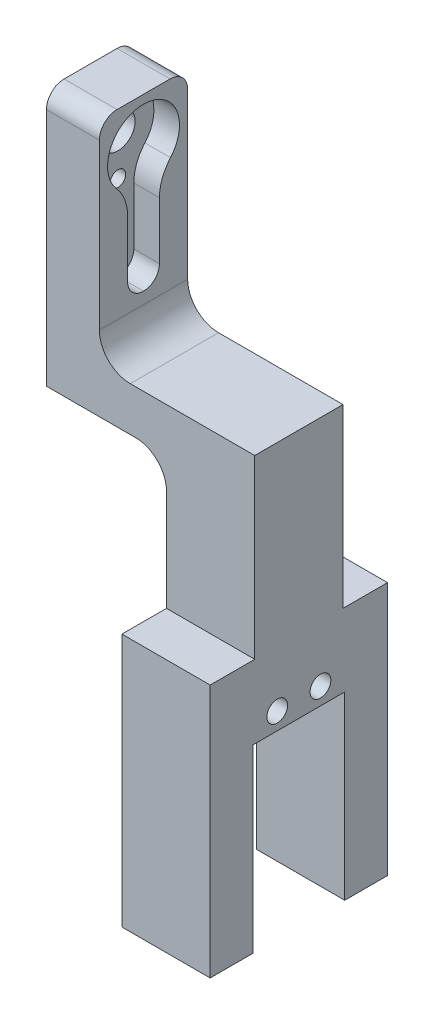
SolidWorks part; units mm, degrees
ref_plane "Front Plane" through (0, 0, 0) normal (0, 0, 1) x (1, 0, 0)
ref_plane "Top Plane" through (0, 0, 0) normal (0, 1, 0) x (1, 0, 0)
ref_plane "Right Plane" through (0, 0, 0) normal (1, 0, 0) x (0, 0, -1)
sketch "Sketch1" plane through (0, 0, 0) normal (1, 0, 0) x (0, 0, -1)
  line L1 (-10, 10) -> (10, 10)
  line L2 (-10, 10) -> (-10, -10)
  line L3 (-10, -10) -> (10, -10)
  line L4 (10, 10) -> (10, -10)
  line L5 (-10, 10) -> (10, -10) construction
  line L6 (-10, -10) -> (10, 10) construction
  point P0 (0, 0)
  dimension "D1" = 20
  dimension "D2" = 20
extrude "Boss-Extrude1" add sketch "Sketch1" along normal blind 20
sketch "Sketch2" plane through (20, 0, 0) normal (1, 0, 0) x (0, 0, -1)
  line L1 (-22.5, 35) -> (22.5, 35)
  line L2 (-22.5, 35) -> (-22.5, -35)
  line L3 (-22.5, -35) -> (22.5, -35)
  line L4 (22.5, 35) -> (22.5, -35)
  line L5 (-22.5, 35) -> (22.5, -35) construction
  line L6 (-22.5, -35) -> (22.5, 35) construction
  point P0 (0, 0)
  dimension "D1" = 45
  dimension "D2" = 70
extrude "Boss-Extrude2" add sketch "Sketch2" along normal blind 12
sketch "Sketch4" plane through (32, 0, 0) normal (1, 0, 0) x (0, 0, -1)
  line L0 (0, 7.65) -> (0, 8.1702) construction
  line L1 (7.65, 7.65) -> (-7.65, 7.65) construction
  line L17 (3.6, -26.55) -> (-3.6, -26.55) construction
  line L18 (-7.65, 7.65) -> (7.65, 7.65) construction
  line L22 (-7.65, 7.65) -> (-7.65, -27.55) construction
  line L23 (-7.65, -27.55) -> (7.65, -27.55) construction
  line L24 (7.65, 7.65) -> (7.65, -27.55) construction
  line L25 (-7.65, 7.65) -> (7.65, -27.55) construction
  line L26 (-7.65, -27.55) -> (7.65, 7.65) construction
  line L27 (3.6, -26.55) -> (3.6, -28.55) construction
  line L28 (3.6, -28.55) -> (-3.6, -28.55) construction
  line L29 (-3.6, -26.55) -> (-3.6, -28.55) construction
  line L30 (3.6, -26.55) -> (-3.6, -28.55) construction
  line L31 (3.6, -28.55) -> (-3.6, -26.55) construction
  line L34 (3.6, -28.55) -> (-3.6, -28.55)
  line L35 (-3.6, -28.55) -> (-3.6, -7.3118)
  line L36 (3.6, -28.55) -> (3.6, -7.3118)
  arc A1 (3.6, -6.75) -> (-3.6, -6.75) centre (0, 0) ccw construction
  arc A2 (3.6, -7.3118) -> (-3.6, -7.3118) centre (0, 0) ccw
  point P1 (0, -27.55)
  point P7 (0, -13.75)
  point P10 (0, 7.65)
  point P14 (0, -9.95)
  dimension "D1" = 15.3
  dimension "D5" = 2
  dimension "D2" = 15.3
  dimension "D3" = 35.2
  dimension "D4" = 7.2
extrude "Cut-Extrude1" cut sketch "Sketch4" against normal blind 5.8
fillet "Fillet1" radius 3.6 2 edges at (29.1, -28.55, 3.6) (29.1, -28.55, -3.6)
fillet "Fillet2" radius 10 2 edges at (29.1, -7.3118, 3.6) (29.1, -7.3118, -3.6)
sketch "Sketch5" plane through (0, 0, 0) normal (-1, 0, 0) x (0, 0, 1)
  circle A0 centre (0, 0) radius 3.9
  dimension "D1" = 7.8
extrude "Cut-Extrude2" cut sketch "Sketch5" against normal through all
sketch "Sketch6" plane through (26.2, 0, 0) normal (1, 0, 0) x (0, 0, -1)
  line L0 (0, -19.35) -> (0, 0) construction
  line L1 (0, -25.65) -> (0, -23.15) construction
  line L2 (0, -23.15) -> (0, -21.85) construction
  line L3 (0, -21.85) -> (0, -19.35) construction
  line L5 (0, 0) -> (1.164, 0) construction
  line L6 (0, 0) -> (0, -9.35) construction
  line L7 (0, -9.35) -> (1.164, -9.35) construction
  line L8 (1.164, 0) -> (1.164, -9.35) construction
  line L9 (0, 0) -> (1.164, -9.35) construction
  line L10 (0, -9.35) -> (1.164, 0) construction
  circle A0 centre (0, -20.6) radius 1.75
  circle A1 centre (0, -9.35) radius 1.75
  point P11 (0.582, -4.675)
  dimension "D5" = 3.5
  dimension "D6" = 9.35
  dimension "D7" = 3.5
  dimension "D1" = 19.35
  dimension "D2" = 2.5
  dimension "D3" = 1.3
  dimension "D4" = 2.5
extrude "Cut-Extrude3" cut sketch "Sketch6" against normal up to next
sketch "Sketch7" plane through (0, -35, 0) normal (0, -1, 0) x (1, 0, 0)
  line L1 (32, 22.5) -> (20, 22.5)
  line L2 (32, 22.5) -> (32, -22.5)
  line L3 (32, -22.5) -> (20, -22.5)
  line L4 (20, 22.5) -> (20, -22.5)
  line L5 (32, 22.5) -> (20, -22.5) construction
  line L6 (32, -22.5) -> (20, 22.5) construction
  point P5 (26, 0)
extrude "Cut-Extrude4" cut sketch "Sketch7" against normal blind 4.8
sketch "Sketch9" plane through (0, 35, 0) normal (0, 1, 0) x (1, 0, 0)
  line L1 (32, 22.5) -> (20, 22.5)
  line L2 (32, 22.5) -> (32, -22.5)
  line L3 (32, -22.5) -> (20, -22.5)
  line L4 (20, 22.5) -> (20, -22.5)
  line L5 (32, 22.5) -> (20, -22.5) construction
  line L6 (32, -22.5) -> (20, 22.5) construction
  point P4 (26, 0)
extrude "Cut-Extrude5" cut sketch "Sketch9" against normal blind 23.8
sketch "Sketch10" plane through (20, 0, 0) normal (-1, 0, 0) x (0, 0, 1)
  line L0 (-22.5, 11.2) -> (22.5, 11.2) construction
  line L1 (-10, 11.2) -> (-22.5, 11.2)
  line L2 (-10, 11.2) -> (-10, -30.2)
  line L3 (-10, -30.2) -> (-22.5, -30.2)
  line L4 (-22.5, 11.2) -> (-22.5, -30.2)
  line L5 (-10, 11.2) -> (-22.5, -30.2) construction
  line L6 (-10, -30.2) -> (-22.5, 11.2) construction
  line L7 (22.5, -30.2) -> (-22.5, -30.2) construction
  line L9 (10, 11.2) -> (22.5, 11.2)
  line L10 (10, 11.2) -> (10, -30.2)
  line L11 (10, -30.2) -> (22.5, -30.2)
  line L12 (22.5, 11.2) -> (22.5, -30.2)
  line L13 (10, 11.2) -> (22.5, -30.2) construction
  line L14 (10, -30.2) -> (22.5, 11.2) construction
  point P4 (-16.25, -9.5)
  point P13 (16.25, -9.5)
extrude "Cut-Extrude6" cut sketch "Sketch10" against normal blind 23.8
sketch "Sketch11" plane through (20, 0, 0) normal (-1, 0, 0) x (0, 0, 1)
  line L5 (-10, 11.2) -> (10, 11.2)
  line L6 (-10, 11.2) -> (-10, 10)
  line L7 (-10, 10) -> (10, 10)
  line L8 (10, 11.2) -> (10, 10)
  line L9 (-10, 11.2) -> (10, 10) construction
  line L10 (-10, 10) -> (10, 11.2) construction
  point P4 (0, 10.6)
extrude "Cut-Extrude7" cut sketch "Sketch11" against normal blind 23.8
sketch "Sketch12" plane through (0, 0, 0) normal (-1, 0, 0) x (0, 0, 1)
  line L1 (10, 10) -> (-10, 10)
  line L2 (10, 10) -> (10, -10)
  line L3 (10, -10) -> (-10, -10)
  line L4 (-10, 10) -> (-10, -10)
  line L5 (10, 10) -> (-10, -10) construction
  line L6 (10, -10) -> (-10, 10) construction
  circle A0 centre (0, 0) radius 3.9
  point P4 (0, 0)
extrude "Boss-Extrude3" add sketch "Sketch12" along normal blind 20
sketch "Sketch13" plane through (-20, 0, 0) normal (-1, 0, 0) x (0, 0, 1)
  line L8 (10.1, -10.1) -> (10.1, 10.1)
  line L9 (10.1, 10.1) -> (-10.1, 10.1)
  line L10 (-10.1, 10.1) -> (-10.1, -10.1)
  line L11 (-10.1, -10.1) -> (10.1, -10.1)
  line L12 (10.1, -10.1) -> (10.1, 10.1)
  line L13 (10.1, 10.1) -> (-10.1, 10.1)
  line L14 (-10.1, 10.1) -> (-10.1, -10.1)
  line L15 (-10.1, -10.1) -> (10.1, -10.1)
  circle A0 centre (0, 0) radius 3.9
  dimension "D1" = 0.1
extrude "Boss-Extrude4" add sketch "Sketch13" against normal up to surface (40 mm away) up to face at (20, -20.6, -1.75)
sketch "Sketch14" plane through (0, 10, 0) normal (0, 1, 0) x (1, 0, 0)
  line L1 (32, 10) -> (20, 10)
  line L2 (32, 10) -> (32, -10)
  line L3 (32, -10) -> (20, -10)
  line L4 (20, 10) -> (20, -10)
  line L5 (32, 10) -> (20, -10) construction
  line L6 (32, -10) -> (20, 10) construction
  point P4 (26, 0)
extrude "Boss-Extrude5" add sketch "Sketch14" along normal blind 0.1
sketch "Sketch17" plane through (-20, 0, 0) normal (-1, 0, 0) x (0, 0, 1)
  circle A0 centre (0, 0) radius 4.8309
extrude "Boss-Extrude8" add sketch "Sketch17" against normal blind 39
sketch "Sketch18" plane through (-20, 0, 0) normal (-1, 0, 0) x (0, 0, 1)
  line L1 (10.1, 10.1) -> (-10.1, 10.1)
  line L2 (10.1, 10.1) -> (10.1, -10.1)
  line L3 (10.1, -10.1) -> (-10.1, -10.1)
  line L4 (-10.1, 10.1) -> (-10.1, -10.1)
  line L5 (10.1, 10.1) -> (-10.1, -10.1) construction
  line L6 (10.1, -10.1) -> (-10.1, 10.1) construction
  point P4 (0, 0)
extrude "Cut-Extrude8" cut sketch "Sketch18" against normal up to surface (40 mm away) up to face at (20, -20.6, -1.75)
fillet "Fillet4" radius 4 2 edges at (26, 10.1, -10) (26, 10.1, 10)
sketch "Sketch20" plane through (0, -30.2, 0) normal (0, -1, 0) x (1, 0, 0)
  line L6 (20, 10) -> (32, 10)
  line L9 (20, 10) -> (20, -10)
  line L10 (20, -10) -> (32, -10)
  line L11 (32, 10) -> (32, -10)
  line L12 (20, 10) -> (32, -10) construction
  line L13 (20, -10) -> (32, 10) construction
  point P4 (26, 0)
extrude "Boss-Extrude9" add sketch "Sketch20" along normal blind 8
sketch "Sketch21" plane through (0, -38.2, 0) normal (0, -1, 0) x (1, 0, 0)
  line L5 (20, 10) -> (67.2, 10)
  line L6 (20, 10) -> (20, -10)
  line L7 (20, -10) -> (67.2, -10)
  line L8 (67.2, 10) -> (67.2, -10)
  line L9 (20, 10) -> (67.2, -10) construction
  line L10 (20, -10) -> (67.2, 10) construction
  point P4 (43.6, 0)
  dimension "D1" = 47.2
extrude "Boss-Extrude11" add sketch "Sketch21" along normal blind 10
sketch "Sketch23" plane through (0, -48.2, 0) normal (0, -1, 0) x (1, 0, 0)
  line L0 (20, -10) -> (67.2, -10) construction
  line L1 (67.2, 10) -> (47.2, 10)
  line L2 (67.2, 10) -> (67.2, -10)
  line L3 (67.2, -10) -> (47.2, -10)
  line L4 (47.2, 10) -> (47.2, -10)
  line L5 (67.2, 10) -> (47.2, -10) construction
  line L6 (67.2, -10) -> (47.2, 10) construction
  point P4 (57.2, 0)
  dimension "D1" = 20
extrude "Boss-Extrude12" add sketch "Sketch23" along normal blind 30
sketch "Sketch25" plane through (0, -78.2, 0) normal (0, -1, 0) x (1, 0, 0)
  line L1 (67.2, 10) -> (47.2, 10) construction
  line L2 (67.2, 10) -> (67.2, -10) construction
  line L3 (67.2, -10) -> (47.2, -10) construction
  line L4 (47.2, 10) -> (47.2, -10) construction
  line L5 (67.2, 10) -> (47.2, -10) construction
  line L6 (67.2, -10) -> (47.2, 10) construction
  line L7 (67.2, 20.1) -> (47.2, 20.1)
  line L8 (67.2, 20.1) -> (67.2, -20.1)
  line L9 (67.2, -20.1) -> (47.2, -20.1)
  line L10 (47.2, 20.1) -> (47.2, -20.1)
  line L11 (67.2, 20.1) -> (47.2, -20.1) construction
  line L12 (67.2, -20.1) -> (47.2, 20.1) construction
  point P4 (57.2, 0)
  point P7 (57.2, 0)
  dimension "D1" = 40.2
extrude "Boss-Extrude13" add sketch "Sketch25" along normal blind 57.5
sketch "Sketch26" plane through (0, -135.7, 0) normal (0, -1, 0) x (1, 0, 0)
  line L1 (67.2, 20.1) -> (47.2, 20.1) construction
  line L2 (67.2, 20.1) -> (67.2, -20.1) construction
  line L3 (67.2, -20.1) -> (47.2, -20.1) construction
  line L4 (47.2, 20.1) -> (47.2, -20.1) construction
  line L5 (67.2, 20.1) -> (47.2, -20.1) construction
  line L6 (67.2, -20.1) -> (47.2, 20.1) construction
  line L7 (67.2, 10.4) -> (47.2, 10.4)
  line L8 (67.2, 10.4) -> (67.2, -10.4)
  line L9 (67.2, -10.4) -> (47.2, -10.4)
  line L10 (47.2, 10.4) -> (47.2, -10.4)
  line L11 (67.2, 10.4) -> (47.2, -10.4) construction
  line L12 (67.2, -10.4) -> (47.2, 10.4) construction
  point P4 (57.2, 0)
  point P7 (57.2, 0)
  dimension "D1" = 20.8
extrude "Cut-Extrude9" cut sketch "Sketch26" against normal blind 40.9
sketch "Sketch27" plane through (0, -135.7, 0) normal (0, -1, 0) x (-1, 0, 0)
  line L0 (-67.2, 10.4) -> (-67.2, -10.4) construction
  line L1 (-67.2, 10.4) -> (-47.2, 10.4) construction
  line L2 (-67.2, 10.4) -> (-67.2, 20.1) construction
  line L3 (-67.2, 20.1) -> (-47.2, 20.1) construction
  line L4 (-47.2, 10.4) -> (-47.2, 20.1) construction
  line L5 (-67.2, 10.4) -> (-47.2, 20.1) construction
  line L6 (-67.2, 20.1) -> (-47.2, 10.4) construction
  line L7 (-67.2, 0) -> (-48.4136, 0) construction
  circle A0 centre (-57.2, 15.25) radius 2.35
  circle A1 centre (-57.2, -15.25) radius 2.35
  point P4 (-57.2, 15.25)
  dimension "D1" = 4.7
extrude "Cut-Extrude10" cut sketch "Sketch27" against normal blind 10
sketch "Sketch28" plane through (47.2, 0, 0) normal (-1, 0, 0) x (0, 0, 1)
  line L0 (0, -94.8) -> (0, -90.91) construction
  line L1 (10.4, -94.8) -> (-10.4, -94.8) construction
  line L2 (0, -90.91) -> (4.9, -90.91) construction
  circle A0 centre (4.9, -90.91) radius 2.35
  circle A1 centre (-4.9, -90.91) radius 2.35
  dimension "D3" = 4.7
  dimension "D1" = 4.9
  dimension "D2" = 3.89
extrude "Cut-Extrude11" cut sketch "Sketch28" against normal through all
chamfer "Chamfer1" distance 1 angle 45 4 edges at (57.2, -135.7, -17.6) (57.2, -135.7, 17.6) (47.2, -90.91, -7.25) (47.2, -90.91, 7.25)
fillet "Fillet5" radius 7 2 edges at (32, -38.2, 0) (47.2, -48.2, 0)
